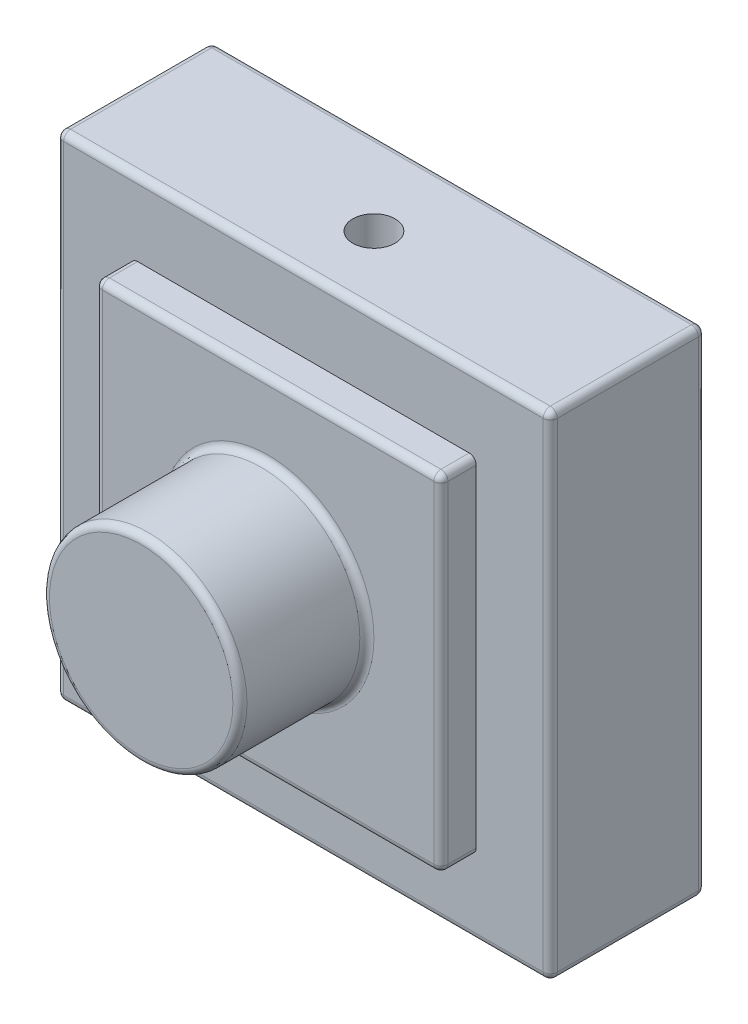
SolidWorks part; units mm, degrees
ref_plane "Front Plane" through (0, 0, 0) normal (0, 0, 1) x (1, 0, 0)
ref_plane "Top Plane" through (0, 0, 0) normal (0, 1, 0) x (1, 0, 0)
ref_plane "Right Plane" through (0, 0, 0) normal (1, 0, 0) x (0, 0, -1)
sketch "Sketch1" plane through (0, 0, 0) normal (0, 0, 1) x (1, 0, 0)
  line L1 (-17.5, 17.5) -> (17.5, 17.5)
  line L2 (-17.5, 17.5) -> (-17.5, -17.5)
  line L3 (-17.5, -17.5) -> (17.5, -17.5)
  line L4 (17.5, 17.5) -> (17.5, -17.5)
  line L5 (-17.5, 17.5) -> (17.5, -17.5) construction
  line L6 (-17.5, -17.5) -> (17.5, 17.5) construction
  point P0 (0, 0)
  dimension "D1" = 35
  dimension "D2" = 35
extrude "Boss-Extrude1" add sketch "Sketch1" along normal blind 11
sketch "Sketch2" plane through (0, 17.5, 0) normal (0, 1, 0) x (1, 0, 0)
  line L0 (0, 0) -> (0, -6) construction
  circle A0 centre (0, -6) radius 1.5
  dimension "D2" = 3
  dimension "D1" = 6
extrude "Cut-Extrude1" cut sketch "Sketch2" against normal blind 5
ref_plane "Plane4" through (0, 0, 0) normal (0, 1, 0) x (1, 0, 0)
mirror "Mirror1" about plane through (0, 0, 0) normal (0, 1, 0) of "Cut-Extrude1"
sketch "Sketch3" plane through (0, 0, 11) normal (0, 0, 1) x (1, 0, 0)
  line L1 (-12.25, 12.25) -> (12.25, 12.25)
  line L2 (-12.25, 12.25) -> (-12.25, -12.25)
  line L3 (-12.25, -12.25) -> (12.25, -12.25)
  line L4 (12.25, 12.25) -> (12.25, -12.25)
  line L5 (-12.25, 12.25) -> (12.25, -12.25) construction
  line L6 (-12.25, -12.25) -> (12.25, 12.25) construction
  point P0 (0, 0)
  dimension "D1" = 24.5
  dimension "D2" = 24.5
extrude "Boss-Extrude2" add sketch "Sketch3" along normal blind 2.5
sketch "Sketch4" plane through (0, 0, 13.5) normal (0, 0, 1) x (1, 0, 0)
  circle A0 centre (0, 0) radius 7
  dimension "D1" = 14
extrude "Boss-Extrude3" add sketch "Sketch4" along normal blind 9
fillet "Fillet1" radius 0.5 21 edges at (17.5, 0, 11) (17.5, 0, 0) (-17.5, 0, 0) (0, 17.5, 0) (0, -17.5, 0) (0, -17.5, 11) (-17.5, 0, 11) (0, 12.25, 13.5) (-12.25, 0, 13.5) (0, -12.25, 13.5) (12.25, 0, 13.5) (-12.25, -12.25, 12.25) (-12.25, 12.25, 12.25) (12.25, -12.25, 12.25) (7, 0, 13.5) (12.25, 12.25, 12.25) (-17.5, -17.5, 5.5) (-17.5, 17.5, 5.5) (17.5, -17.5, 5.5) (17.5, 17.5, 5.5) (0, 17.5, 11)
fillet "Fillet2" radius 0.5 1 edges at (7, 0, 22.5)
ref_plane "Plane5" through (0, 0, 22.5) normal (0, 0, 1) x (1, 0, 0)
ref_plane "Plane6" [suppressed] through (0, 0, 2022.5) normal (0, 0, 1) x (1, 0, 0)
sketch "Sketch5" [suppressed] plane through (0, 0, 0) normal (1, 0, 0) x (0, 0, -1)
  line L0 (-22.5, 0) -> (-2022.5, 0) construction
  line L1 (-22.5, 7.15) -> (-22.5, -7.15) construction
  line L2 (-22.5, 0) -> (-2022.5, -3464.1016) construction
  line L3 (-2022.5, -3464.1016) -> (-2022.5, 0) construction
  dimension "D1" = 60
  dimension "D2" = 2000
ref_plane "Plane7" [suppressed] through (0, 0, 2022.5) normal (0, 0, 1) x (1, 0, 0)
sketch "Sketch8" [suppressed] plane through (0, 0, 2022.5) normal (0, 0, 1) x (1, 0, 0)
  line L1 (-4839.2071, 3464.1016) -> (4839.2071, 3464.1016)
  line L2 (-4839.2071, 3464.1016) -> (-4839.2071, -3464.1016)
  line L3 (-4839.2071, -3464.1016) -> (4839.2071, -3464.1016)
  line L4 (4839.2071, 3464.1016) -> (4839.2071, -3464.1016)
  line L5 (-4839.2071, 3464.1016) -> (4839.2071, -3464.1016) construction
  line L6 (-4839.2071, -3464.1016) -> (4839.2071, 3464.1016) construction
  point P0 (0, 0)
  dimension "D1" = 9678.4142
sketch "Sketch9" plane through (0, 0, 0) normal (1, 0, 0) x (0, 0, -1)
  line L0 (-22.5, 0) -> (-54.0248, 0) construction
  line L1 (-22.5, 7.15) -> (-22.5, -7.15) construction
  line L2 (-22.5, 0) -> (-55.8883, 57.8303) construction
  line L3 (-22.5, 0) -> (-54.1365, -54.796) construction
  dimension "D1" = 60
  dimension "D2" = 60
sketch "Sketch10" plane through (0, 0, 0) normal (0, 1, 0) x (1, 0, 0)
  line L0 (0, -22.5) -> (-51.5419, -52.2577) construction
  line L1 (0, -22.5) -> (0, -54.1365) construction
  line L2 (-7.15, -22.5) -> (7.15, -22.5) construction
  line L3 (0, -22.5) -> (58.55, -56.3038) construction
  dimension "D1" = 60
  dimension "D2" = 60
